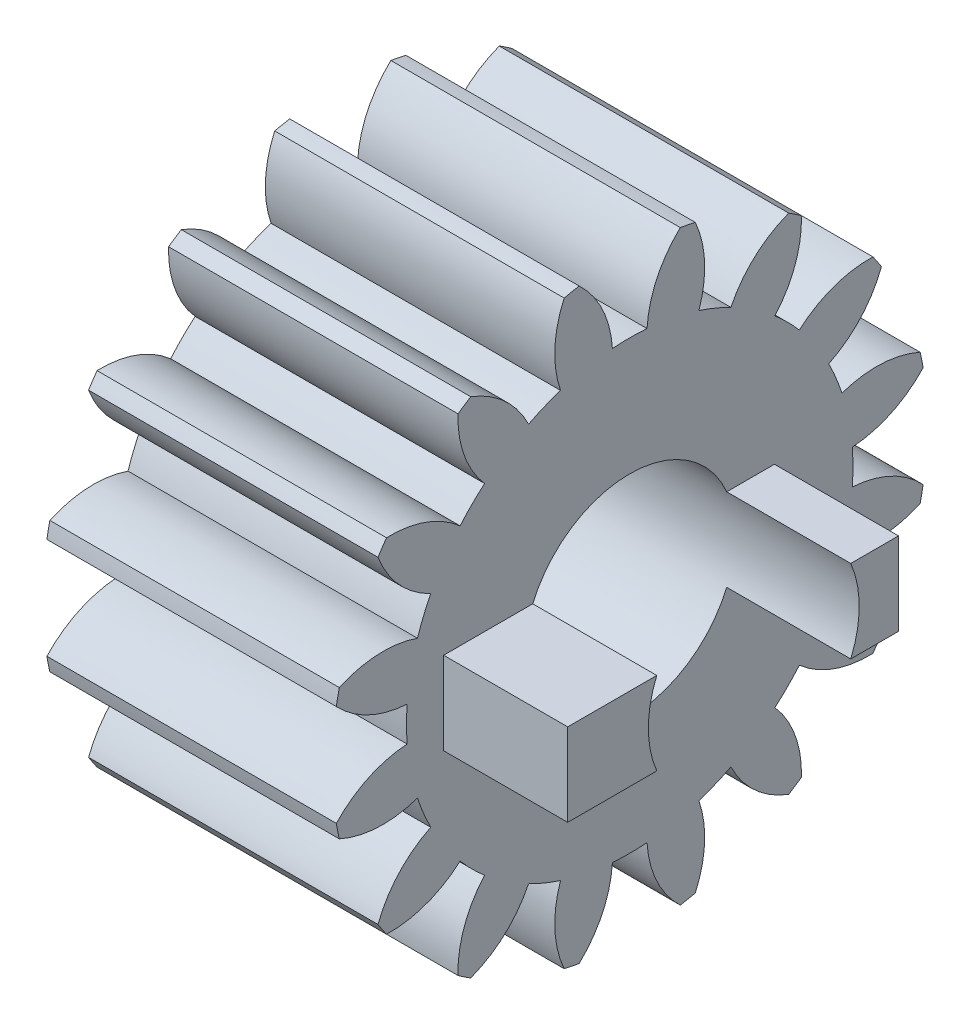
SolidWorks part; units mm, degrees
ref_plane "Plane1" through (0, 0, 0) normal (0, 0, 1) x (1, 0, 0)
ref_plane "Plane2" through (0, 0, 0) normal (0, 1, 0) x (1, 0, 0)
ref_plane "Plane3" through (0, 0, 0) normal (1, 0, 0) x (0, 0, -1)
other "Configuration Table"
sketch "HoldingSke" plane through (0, 0, 0) normal (0, 1, 0) x (1, 0, 0)
  line L0 (0, 0) -> (1.2016, -0.3445)
  line L1 (-15, 0) -> (100, 0) construction
  line L2 (0, 0) -> (-2.1039, 2.3779)
  line L3 (0, 0) -> (-11.863, 4.5341)
  line L4 (0, 0) -> (8.3015, 2.3804)
  line L5 (0, 0) -> (-46.8476, -17.4728)
  line L6 (0, 0) -> (-5.8027, -3.9151)
  line L7 (-2.1039, 2.3779) -> (8.6586, 51.2059)
  line L8 (-76.2, 54.61) -> (-76.1, 54.61)
  line L9 (-71.009, 38.7566) -> (-53.1078, 45.2721)
  line L10 (-76.2, 71.12) -> (104.1128, 71.12)
  line L11 (0, 0) -> (-7, 0)
  line L12 (-76.2, 101.6) -> (-76.17, 101.6)
  line L13 (24.9733, 27.94) -> (52.9518, 28.4284)
  line L14 (24.9733, 27.94) -> (24.9743, 27.94)
  line L15 (24.9733, 27.94) -> (100.4006, 29.5858)
  line L16 (-63.627, -0.8) -> (-12.827, -0.8)
  circle A0 centre (0, 0) radius 0.5
  circle A1 centre (0, 0) radius 5.399
  circle A2 centre (0, 0) radius 37.5
  circle A3 centre (0, 0) radius 0.5
  dimension "MHD" = 10.798
  dimension "Hub_dia" = 75
  dimension "Bore" = 1
  dimension "MBD" = 1
  dimension "Num_teeth" = 16
  dimension "Pitch" = 1.25
  dimension "Overall_len" = 50
  dimension "Show_teeth" = 16
  dimension "Thickness" = 7
  dimension "OAL" = 50.0001
  dimension "T_dim" = 0.1
  dimension "Ap" = 20
  dimension "H" = 19.05
  dimension "Pitch_radius" = 180.3128
  dimension "Width" = 7
  dimension "Backlash" = 0.03
  dimension "Addendum_fac" = 1
  dimension "Dedendum_fac" = 1.25
  dimension "Clearance_fac" = 0.25
  dimension "Dedendum_add" = 0.001
  dimension "Module" = 0.8
sketch "BasProSke" plane through (0, 0, 0) normal (0, 1, 0) x (1, 0, 0)
  line L0 (-10, 0) -> (60, 0) construction
  line L1 (0, 0) -> (0, 7.2)
  line L2 (0, 0) -> (7, 0)
  line L3 (7, 0) -> (7, 7.2)
  line L4 (7, 7.2) -> (0, 7.2)
  dimension "Thickness" = 7
  dimension "Diameter" = 14.4
revolve "Base-Revolve" add sketch "BasProSke" angle 360 about L0
sketch "TooCutSke" plane through (0, 0, 0) normal (1, 0, 0) x (0, 0, -1)
  line L1 (0, 0) -> (0, 107) construction
  line L2 (0, 0) -> (-0.6798, 6.3638) construction
  line L3 (0, 0) -> (-2.4871, 12.5033) construction
  line L4 (-0.6798, 6.3638) -> (-1.2435, 6.2517) construction
  arc A0 (0.4184, 5.3828) -> (-0.4184, 5.3828) centre (0, 0) ccw
  arc A1 (1.2466, 7.117) -> (-1.2466, 7.117) centre (0, 0) ccw
  circle A2 centre (0, 0) radius 6.4 construction
  circle A3 centre (0, 0) radius 6.014 construction
  arc A4 (-0.4184, 5.3828) -> (-1.2466, 7.117) centre (-2.9737, 5.2274) ccw
  arc A5 (1.2466, 7.117) -> (0.4184, 5.3828) centre (2.9737, 5.2274) ccw
  dimension "Root_dia" = 10.798
  dimension "Overcut_dia" = 14.4508
  dimension "Pitch_dia" = 12.8
  dimension "Base_dia" = 12.0281
  dimension "Flank_rad" = 2.56
  dimension "Half_ang" = 11.25
  dimension "Half_CT" = 0.5748
extrude "ToothCut" cut sketch "TooCutSke" along normal through all
fillet "Breaks" [suppressed] radius 0.016 tangent propagation no
fillet "RootFillets" [suppressed] radius 0.201
pattern_circular "TeethCuts" count 16 every 22.5 about axis through (-10, 0, 0) along (1, 0, 0) of "ToothCut", "RootFillets", "Breaks"
sketch "HubNeaOneSke" plane through (0, 0, 0) normal (-1, 0, 0) x (0, 0, 1)
  circle A0 centre (0, 0) radius 5.399
  dimension "Diameter" = 10.798
extrude "HubNearOne" [suppressed] add sketch "HubNeaOneSke" along normal blind 43.0001
sketch "HubNeaBotSke" plane through (0, 0, 0) normal (-1, 0, 0) x (0, 0, 1)
  circle A0 centre (0, 0) radius 5.399
  dimension "Diameter" = 10.798
extrude "HubNearBoth" [suppressed] add sketch "HubNeaBotSke" along normal blind 21.5
ref_plane "FarPln" through (7, 0, 0) normal (1, 0, 0) x (0, 0, -1)
sketch "HubFarSke" plane through (7, 0, 0) normal (1, 0, 0) x (0, 0, -1)
  circle A0 centre (0, 0) radius 5.399
  dimension "Diameter" = 10.798
extrude "HubFar" [suppressed] add sketch "HubFarSke" along normal blind 21.5
sketch "BorSke" plane through (0, 0, 0) normal (1, 0, 0) x (0, 0, -1)
  circle A0 centre (0, 0) radius 0.5
  dimension "Diameter" = 1
extrude "Bore" cut sketch "BorSke" along normal mid plane 100.0001
sketch "KeySke" plane through (0, 0, 0) normal (1, 0, 0) x (0, 0, -1)
  line L0 (-0.05, 0) -> (-0.05, 0.6)
  line L1 (-0.05, 0.6) -> (0.05, 0.6)
  line L2 (0.05, 0.6) -> (0.05, 0)
  line L3 (0, 0) -> (0, 34) construction
  line L4 (-0.05, 0) -> (0.05, 0)
  dimension "Offset" = 0.6
  dimension "Width" = 0.1
extrude "Keyway" [suppressed] cut sketch "KeySke" along normal mid plane 100.0001
pattern_circular "Keyway2" [suppressed] count 2 every 90 about axis through (-10, 0, 0) along (1, 0, 0) reverse direction yes
ref_axis "基准轴1" through (0, 0, 0) along (1, 0, 0)
sketch "草图1" plane through (0, 0, 0) normal (1, 0, 0) x (0, 0, -1)
  circle A0 centre (0, 0) radius 2.55
  dimension "D1" = 5.1
extrude "切除-拉伸1" cut sketch "草图1" along normal through all
sketch "草图2" plane through (7, 0, 0) normal (-1, 0, 0) x (0, 0, 1)
  line L0 (0, 0) -> (4.5, 0) construction
  line L1 (0, 0) -> (-3.5, 0) construction
  line L2 (4.5, -1) -> (-3.5, -1)
  line L3 (4.5, -1) -> (4.5, 1)
  line L4 (4.5, 1) -> (-3.5, 1)
  line L6 (-3.5, 1) -> (-3.5, -1)
  circle A0 centre (0, 0) radius 2.55 construction
  circle A1 centre (0, 0) radius 2.55
  point P7 (4.5, 0)
  point P10 (-3.5, 0)
  dimension "D1" = 3.5
  dimension "D2" = 2
  dimension "D4" = 4.5
extrude "凸台-拉伸1" add sketch "草图2" against normal blind 3 contours L4 A1 L2 L6 | L2 A1 L4 L3 region at (7, 0, 3.4906) region at (7, 0, -2.9897)
equation "' \"Module@HoldingSke\" = 6.35"
equation "' \"Num_teeth@HoldingSke\" = 12"
equation "' \"Ap@HoldingSke\" =  20"
equation "' \"Ap@HoldingSke\" = 20"
equation "' \"Width@HoldingSke\" = 0.5 * 25.4"
equation "' \"Hub_dia@HoldingSke\"= 1 * 25.4"
equation "' \"Hub_dia@HoldingSke\" = 1 * 25.4"
equation "' \"Overall_len@HoldingSke\" = 1.0 * 25.4"
equation "' \"Bore@HoldingSke\" = 0.75 * 25.4"
equation "' \"T_dim@HoldingSke\" = 0.1 * 25.4"
equation "' \"Width@KeySke\" = 0.25 * 25.4"
equation "' \"Show_teeth@HoldingSke\" = 13"
equation "' \"Backlash@HoldingSke\" = 0.009 * 25.4"
equation "' \"Addendum_fac@HoldingSke\" = 1.0"
equation "' \"Dedendum_fac@HoldingSke\" = 1.25"
equation "' \"Dedendum_add@HoldingSke\" = 0.00005 * 25.4"
equation "' \"Clearance_fac@HoldingSke\" = 0.25"
equation "\"Pitch@HoldingSke\" = 1 / \"Module@HoldingSke\""
equation "\"Overcut_dia@TooCutSke\" = (\"Num_teeth@HoldingSke\" + 2 * \"Addendum_fac@HoldingSke\") / \"Pitch@HoldingSke\" + 0.002 * 25.4"
equation "\"Pitch_dia@TooCutSke\" = \"Num_teeth@HoldingSke\" / \"Pitch@HoldingSke\""
equation "\"Base_dia@TooCutSke\" = \"Num_teeth@HoldingSke\" / \"Pitch@HoldingSke\" * cos((\"Ap@HoldingSke\"  * 3.14159265 / 180))"
equation "\"Root_dia@TooCutSke\" = (\"Num_teeth@HoldingSke\" + 2) / \"Pitch@HoldingSke\" - 2 * (\"Addendum_fac@HoldingSke\" + \"Dedendum_fac@HoldingSke\") / \"Pitch@HoldingSke\" - \"Dedendum_add@HoldingSke\" * 2"
equation "\"Half_ang@TooCutSke\" = 180 / \"Num_teeth@HoldingSke\""
equation "\"Half_CT@TooCutSke\" = \"Num_teeth@HoldingSke\" / \"Pitch@HoldingSke\" * sin((3.14159265 / 2 / \"Num_teeth@HoldingSke\")) / 2 - 7 * \"Backlash@HoldingSke\" / 4"
equation "\"Flank_rad@TooCutSke\" = \"Num_teeth@HoldingSke\" / \"Pitch@HoldingSke\" / 5"
equation "\"Radius@RootFillets\" = \"Clearance_fac@HoldingSke\" / \"Pitch@HoldingSke\" + \"Dedendum_add@HoldingSke\""
equation "\"Break_rad@Breaks\" = 0.02 / \"Pitch@HoldingSke\""
equation "\"Thickness@HoldingSke\" = \"Width@HoldingSke\""
equation "\"OAL@HoldingSke\" = \"Thickness@HoldingSke\""
equation "\"MHD@HoldingSke\" = (\"Num_teeth@HoldingSke\" + 2) / \"Pitch@HoldingSke\" - 2 * (\"Addendum_fac@HoldingSke\" + \"Dedendum_fac@HoldingSke\")  / \"Pitch@HoldingSke\" - \"Dedendum_add@HoldingSke\" * 2"
equation "\"MBD@HoldingSke\" = (\"Num_teeth@HoldingSke\" + 2) / \"Pitch@HoldingSke\" - 2 * (\"Addendum_fac@HoldingSke\" + \"Dedendum_fac@HoldingSke\")  / \"Pitch@HoldingSke\" - \"Dedendum_add@HoldingSke\" * 2 - 0.002 * 25.4"
equation "\"MHD@HoldingSke\" = ((sgn( \"MHD@HoldingSke\" - \"Hub_dia@HoldingSke\" )-1)*( \"MHD@HoldingSke\" - \"Hub_dia@HoldingSke\" ))/-2+ \"Hub_dia@HoldingSke\""
equation "\"MBD@HoldingSke\" = ((sgn( \"MBD@HoldingSke\" - \"Bore@HoldingSke\" )-1)*( \"MBD@HoldingSke\" - \"Bore@HoldingSke\" ))/-2+ \"Bore@HoldingSke\""
equation "\"OAL@HoldingSke\" = ((sgn( \"OAL@HoldingSke\" - \"Overall_len@HoldingSke\" )+1)*( \"OAL@HoldingSke\" - \"Overall_len@HoldingSke\" ))/2 + \"Overall_len@HoldingSke\" + 0.000002 * 25.4"
equation "\"Num_teeth@TeethCuts\" = int( \"Show_teeth@HoldingSke\" ) + 1"
equation "\"Num_teeth@TeethCuts\" = ((sgn( \"Num_teeth@TeethCuts\" - \"Num_teeth@HoldingSke\" )-1)*( \"Num_teeth@TeethCuts\" - \"Num_teeth@HoldingSke\" ))/-2+ \"Num_teeth@HoldingSke\""
equation "\"Num_teeth@TeethCuts\" = ((sgn( \"Num_teeth@TeethCuts\" - 2.0)+1)*( \"Num_teeth@TeethCuts\" - 2.0))/2 +2.0"
equation "\"Angle@TeethCuts\" = 360.0 / \"Num_teeth@HoldingSke\""
equation "\"Diameter@BasProSke\" = (\"Num_teeth@HoldingSke\" + 2 * \"Addendum_fac@HoldingSke\") / \"Pitch@HoldingSke\""
equation "\"Thickness@BasProSke\"  = \"Thickness@HoldingSke\""
equation "' \"Fillet_rad@BasProSke\" =  \"Thickness@HoldingSke\" * 0.05"
equation "' \"Fillet_rad@BasProSke\" = \"Thickness@HoldingSke\" * 0.05"
equation "\"MHD@HoldingSke\" = ((sgn( \"MHD@HoldingSke\" - \"Root_dia@TooCutSke\" )-1)*( \"MHD@HoldingSke\" - \"Root_dia@TooCutSke\" ))/-2+ \"Root_dia@TooCutSke\""
equation "\"Diameter@HubNeaOneSke\" = \"MHD@HoldingSke\""
equation "\"Length@HubNearOne\" = \"OAL@HoldingSke\" - \"Thickness@BasProSke\""
equation "\"Diameter@HubNeaBotSke\" = \"MHD@HoldingSke\""
equation "\"Length@HubNearBoth\" = ( \"OAL@HoldingSke\" - \"Thickness@BasProSke\" ) / 2.0"
equation "\"Thickness@FarPln\" = \"Thickness@BasProSke\""
equation "\"Diameter@HubFarSke\" = \"MHD@HoldingSke\""
equation "\"Length@HubFar\" = ( \"OAL@HoldingSke\" - \"Thickness@BasProSke\" ) / 2.0"
equation "\"Diameter@BorSke\" = \"MBD@HoldingSke\""
equation "\"D1@Bore\" = \"OAL@HoldingSke\" * 2.0"
equation "\"D1@Keyway\" = \"OAL@HoldingSke\" * 2.0"
equation "\"Offset@KeySke\" = \"T_dim@HoldingSke\" + \"MBD@HoldingSke\" / 2.0"
